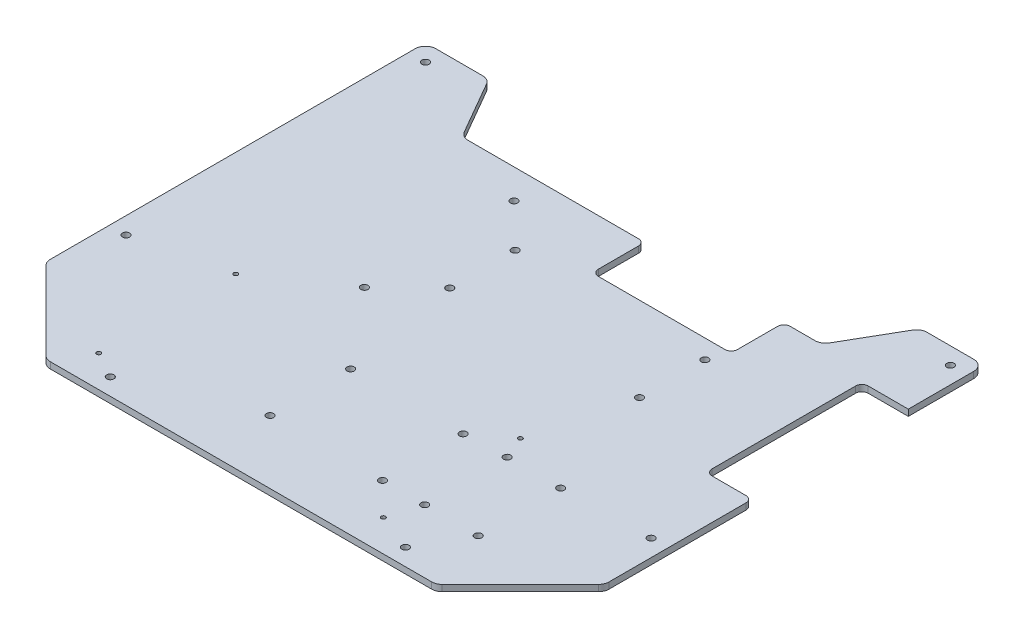
SolidWorks part; units mm, degrees
material "Acier non allié"
ref_plane "Front" through (0, 0, 0) normal (0, 0, 1) x (1, 0, 0)
ref_plane "Top" through (0, 0, 0) normal (0, 1, 0) x (1, 0, 0)
ref_plane "Right" through (0, 0, 0) normal (1, 0, 0) x (0, 0, -1)
sketch "Esquisse1" plane through (0, 0, 0) normal (0, 1, 0) x (1, 0, 0)
  line L0 (0, 0) -> (0, 190) construction
  line L1 (-92.5, 0) -> (92.5, 0)
  line L2 (92.5, 0) -> (132.5, 40)
  line L3 (132.5, 40) -> (132.5, 220)
  line L4 (132.5, 220) -> (102.5, 220)
  line L5 (102.5, 220) -> (85.1795, 190)
  line L6 (85.1795, 190) -> (-85.1795, 190)
  line L7 (-102.5, 220) -> (-85.1795, 190)
  line L8 (-132.5, 220) -> (-102.5, 220)
  line L9 (-132.5, 40) -> (-132.5, 220)
  line L10 (-92.5, 0) -> (-132.5, 40)
  dimension "D1" = 132.5
  dimension "D2" = 220
  dimension "D3" = 60
  dimension "D4" = 30
  dimension "D5" = 40
  dimension "D6" = 40
  dimension "D7" = 30
extrude "Boss.-Extru.1" add sketch "Esquisse1" along normal blind 3
fillet "Congé1" radius 5 10 edges at (92.5, 1.5, 0) (132.5, 1.5, -40) (132.5, 1.5, -220) (102.5, 1.5, -220) (85.1795, 1.5, -190) (-85.1795, 1.5, -190) (-102.5, 1.5, -220) (-132.5, 1.5, -220) (-92.5, 1.5, 0) (-132.5, 1.5, -40)
sketch "Esquisse2" plane through (0, 3, 0) normal (0, 1, 0) x (1, 0, 0)
  line L0 (0, 0) -> (0, 294.1173) construction
  line L2 (-90.4289, 0) -> (90.4289, 0) construction
  circle A0 centre (70, 8) radius 1
  circle A1 centre (124.5, 70) radius 1
  circle A2 centre (124.5, 212) radius 1
  circle A3 centre (-124.5, 212) radius 1
  circle A4 centre (-124.5, 70) radius 1
  circle A5 centre (-70, 8) radius 1
  dimension "D2" = 2
  dimension "D6" = 2
  dimension "D9" = 2
  dimension "D1" = 70
  dimension "D3" = 8
  dimension "D4" = 124.5
  dimension "D5" = 70
  dimension "D7" = 124.5
  dimension "D8" = 212
extrude "Enlèv. mat.-Extru.1" cut sketch "Esquisse2" against normal blind 3
hole_wizard "Dégagement M31" positions "Esquisse3" profile "Esquisse4" hole size "M3" standard "ISO" end condition through all
sketch "Esquisse3" plane through (0, 3, 0) normal (0, 1, 0) x (1, 0, 0)
  point P0 (70, 8)
  point P3 (-70, 8)
  point P6 (-124.5, 70)
  point P9 (-124.5, 212)
  point P12 (124.5, 212)
  point P15 (124.5, 70)
sketch "Esquisse4" plane through (70, 3, -8) normal (1, 0, 0) x (0, 0, 1)
  line L0 (0, 0) -> (0, 3)
  line L1 (0, 3) -> (1.7, 3)
  line L2 (1.7, 3) -> (1.7, 0)
  line L5 (1.7, 0) -> (0, 0)
  line L11 (0, -6.35) -> (0, 107.95) construction
  dimension "Diamètre du perçage jusqu'au prochain" = 3.4
  dimension "Profondeur du perçage jusqu'au prochain" = 3
sketch "Esquisse5" plane through (0, 3, 0) normal (0, 1, 0) x (1, 0, 0)
  line L0 (82.2927, 190) -> (-82.2927, 190) construction
  line L1 (67.5, 190) -> (1.5, 190)
  line L2 (67.5, 190) -> (67.5, 165)
  line L3 (67.5, 165) -> (1.5, 165)
  line L4 (1.5, 190) -> (1.5, 165)
  line L5 (132.5, 42.0711) -> (132.5, 215) construction
  line L6 (132.5, 184) -> (110.5, 184)
  line L7 (132.5, 184) -> (132.5, 110)
  line L8 (132.5, 110) -> (110.5, 110)
  line L9 (110.5, 184) -> (110.5, 110)
  line L10 (127.5, 220) -> (105.3868, 220) construction
  dimension "D1" = 25
  dimension "D2" = 65
  dimension "D3" = 131
  dimension "D4" = 36
  dimension "D5" = 110
  dimension "D6" = 22
extrude "Enlèv. mat.-Extru.2" cut sketch "Esquisse5" against normal through all
fillet "Congé2" radius 3 7 edges at (132.5, 1.5, -110) (110.5, 1.5, -110) (110.5, 1.5, -184) (67.5, 1.5, -190) (67.5, 1.5, -165) (1.5, 1.5, -165) (1.5, 1.5, -190)
sketch "Esquisse6" plane through (0, 3, 0) normal (0, 1, 0) x (1, 0, 0)
  line L0 (110.5, 140.5) -> (-167.6757, 140.5) construction
  line L1 (110.5, 181) -> (110.5, 113) construction
  line L2 (-90.4289, 0) -> (90.4289, 0) construction
  line L3 (110.5, 181) -> (110.5, 113) construction
  circle A0 centre (64, 156) radius 1
  circle A1 centre (-26, 156) radius 1
  circle A2 centre (-46.5, 176) radius 1
  circle A3 centre (64, 125) radius 1
  circle A4 centre (-26, 125) radius 1
  circle A5 centre (-46.5, 105) radius 1
  dimension "D4" = 2
  dimension "D6" = 2
  dimension "D10" = 2
  dimension "D1" = 140.5
  dimension "D2" = 46.5
  dimension "D3" = 15.5
  dimension "D5" = 136.5
  dimension "D7" = 15.5
  dimension "D8" = 35.5
  dimension "D9" = 157
extrude "Enlèv. mat.-Extru.3" cut sketch "Esquisse6" against normal through all
hole_wizard "Dégagement M32" positions "Esquisse7" profile "Esquisse8" hole size "M3" standard "ISO"
sketch "Esquisse7" plane through (0, 3, 0) normal (0, 1, 0) x (1, 0, 0)
  point P0 (-46.5, 105)
  point P3 (-26, 125)
  point P6 (-26, 156)
  point P9 (-46.5, 176)
  point P12 (64, 156)
  point P15 (64, 125)
sketch "Esquisse8" plane through (-46.5, 3, -105) normal (1, 0, 0) x (0, 0, 1)
  line L0 (0, 0) -> (0, 11.0215)
  line L1 (0, 11.0215) -> (1.7, 10)
  line L2 (1.7, 10) -> (1.7, 0)
  line L5 (1.7, 0) -> (0, 0)
  line L10 (0, 11.0215) -> (-1.7, 10) construction
  line L11 (0, -6.35) -> (0, 107.95) construction
  dimension "Diamètre du perçage" = 3.4
  dimension "Profondeur du perçage" = 10
  dimension "Angle de pointe" = 118
sketch "Esquisse9" plane through (0, 3, 0) normal (0, 1, 0) x (1, 0, 0)
  line L0 (132.5, 42.0711) -> (132.5, 107) construction
  line L1 (-90.4289, 0) -> (90.4289, 0) construction
  line L3 (37.1, 30) -> (-16.24, 30) construction
  line L4 (37.1, 30) -> (37.1, 68.24) construction
  line L5 (37.1, 68.24) -> (-16.24, 68.24) construction
  line L6 (-16.24, 30) -> (-16.24, 68.24) construction
  circle A0 centre (82.5, 30) radius 1
  circle A1 centre (57.1, 30) radius 1
  circle A2 centre (57.1, 69.12) radius 1
  circle A3 centre (82.5, 69.12) radius 1
  circle A6 centre (-16.24, 68.24) radius 1
  circle A7 centre (37.1, 68.24) radius 1
  circle A8 centre (37.1, 30) radius 1
  circle A9 centre (-16.24, 30) radius 1
  dimension "D1" = 2
  dimension "D2" = 2
  dimension "D3" = 2
  dimension "D4" = 2
  dimension "D17" = 2
  dimension "D18" = 2
  dimension "D19" = 2
  dimension "D20" = 2
  dimension "D5" = 50
  dimension "D6" = 50
  dimension "D7" = 25.4
  dimension "D8" = 25.4
  dimension "D9" = 39.12
  dimension "D10" = 39.12
  dimension "D11" = 30
  dimension "D12" = 30
  dimension "D13" = 38.24
  dimension "D14" = 53.34
  dimension "D15" = 30
  dimension "D16" = 20
extrude "Enlèv. mat.-Extru.4" cut sketch "Esquisse9" against normal through all
hole_wizard "Dégagement M33" positions "Esquisse10" profile "Esquisse11" hole size "M3" standard "ISO"
sketch "Esquisse10" plane through (0, 3, 0) normal (0, 1, 0) x (1, 0, 0)
  point P0 (57.1, 30)
  point P3 (82.5, 30)
  point P6 (57.1, 69.12)
  point P9 (82.5, 69.12)
sketch "Esquisse11" plane through (57.1, 3, -30) normal (1, 0, 0) x (0, 0, 1)
  line L0 (0, 0) -> (0, 11.0215)
  line L1 (0, 11.0215) -> (1.7, 10)
  line L2 (1.7, 10) -> (1.7, 0)
  line L5 (1.7, 0) -> (0, 0)
  line L10 (0, 11.0215) -> (-1.7, 10) construction
  line L11 (0, -6.35) -> (0, 107.95) construction
  dimension "Diamètre du perçage" = 3.4
  dimension "Profondeur du perçage" = 10
  dimension "Angle de pointe" = 118
sketch "Esquisse12" plane through (0, 3, 0) normal (0, 1, 0) x (1, 0, 0)
  line L0 (-90.4289, 0) -> (90.4289, 0) construction
  line L1 (132.5, 42.0711) -> (132.5, 107) construction
  circle A0 centre (52.5, 15) radius 1
  circle A1 centre (52.5, 80) radius 1
  circle A2 centre (-82.5, 80) radius 1
  circle A3 centre (-82.5, 15) radius 1
  point P12 (0, 0)
  point P13 (0, 0)
  dimension "D5" = 2
  dimension "D6" = 2
  dimension "D7" = 2
  dimension "D8" = 2
  dimension "D1" = 15
  dimension "D2" = 15
  dimension "D3" = 80
  dimension "D4" = 135
  dimension "D9" = 80
  dimension "D10" = 135
  dimension "D11" = 65
  dimension "D12" = 65
extrude "Enlèv. mat.-Extru.5" cut sketch "Esquisse12" against normal through all and the other way through all
hole_wizard "Dégagement M34" positions "Esquisse13" profile "Esquisse14" hole size "M3" standard "ISO"
sketch "Esquisse13" plane through (0, 3, 0) normal (0, 1, 0) x (1, 0, 0)
  point P3 (-16.24, 68.24)
  point P6 (-16.24, 30)
  point P9 (37.1, 30)
  point P12 (37.1, 68.24)
sketch "Esquisse14" plane through (-16.24, 3, -68.24) normal (1, 0, 0) x (0, 0, 1)
  line L0 (0, 0) -> (0, 11.0215)
  line L1 (0, 11.0215) -> (1.7, 10)
  line L2 (1.7, 10) -> (1.7, 0)
  line L5 (1.7, 0) -> (0, 0)
  line L10 (0, 11.0215) -> (-1.7, 10) construction
  line L11 (0, -6.35) -> (0, 107.95) construction
  dimension "Diamètre du perçage" = 3.4
  dimension "Profondeur du perçage" = 10
  dimension "Angle de pointe" = 118
equation "\"WIDTH\"= 300mm'Total width of the robot"
equation "\"LENGTH\"= 220mm'Total length of the robot"
equation "\"CUT_DEPTH\"= 45mm'Depth of the cut on the edges of the plate"
equation "\"Plate_th\"= 3mm'Thickness of the plate"
equation "\"D1\"= \"Plate_th\""
